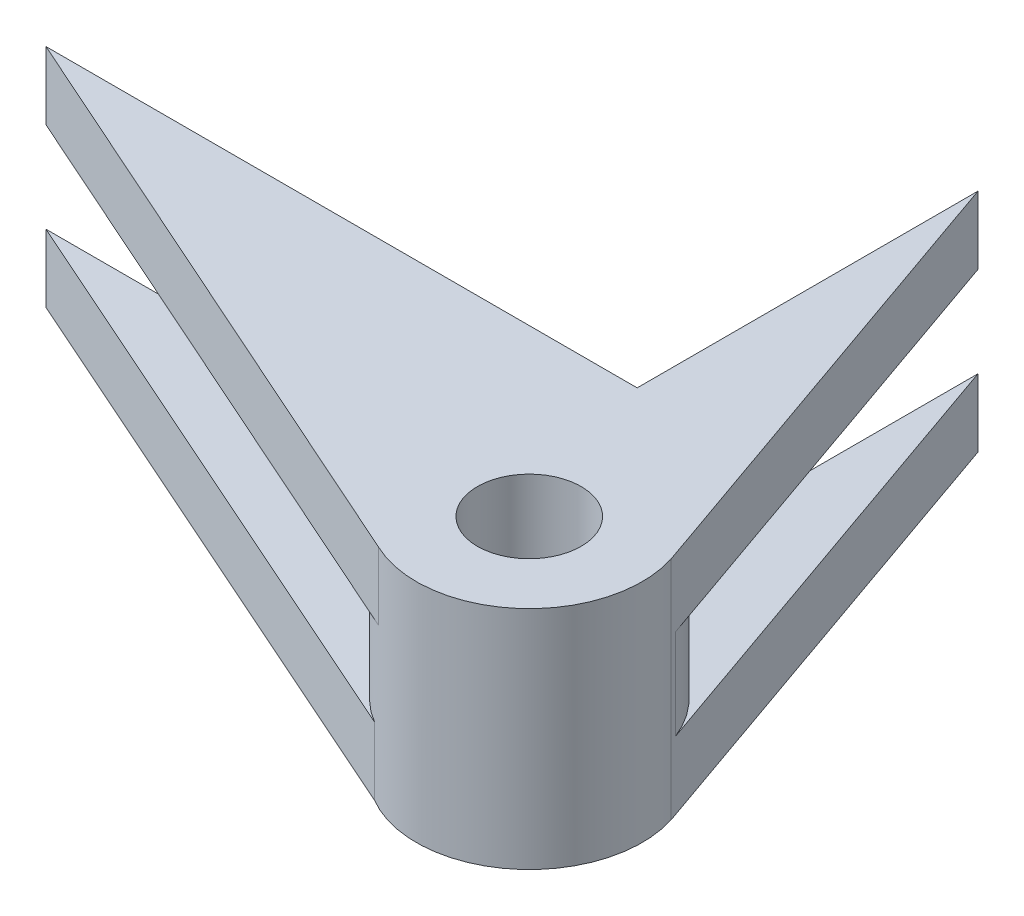
SolidWorks part; units mm, degrees
ref_plane "Front Plane" through (0, 0, 0) normal (0, 0, 1) x (1, 0, 0)
ref_plane "Top Plane" through (0, 0, 0) normal (0, 1, 0) x (1, 0, 0)
ref_plane "Right Plane" through (0, 0, 0) normal (1, 0, 0) x (0, 0, -1)
sketch "Sketch1" plane through (0, 0, 0) normal (0, 1, 0) x (1, 0, 0)
  line L0 (30.5988, 30.1673) -> (30.5988, 0)
  line L1 (30.5988, 30.1673) -> (45.2163, -11.6217)
  line L2 (0, 0) -> (-21.7254, 0)
  line L3 (-21.7254, 0) -> (30.5988, -23.2433)
  line L4 (30.5988, 0) -> (0, 0)
  circle A0 centre (35.6797, -14.6303) radius 10
  circle A1 centre (35.6797, -14.6303) radius 4.5901
  dimension "20" = 20
extrude "Boss-Extrude1" add sketch "Sketch1" along normal blind 6 contours A0 L2 L3 region at (18.2565, 0, 3.1434)
extrude "Boss-Extrude2" add sketch "Sketch1<3>" along normal blind 20 contours A0 A1 region at (44.8474, 0, 11.4234)
sketch "Sketch1<3>" plane through (0, 0, 0) normal (0, 1, 0) x (1, 0, 0) same geometry as "Sketch1"
sketch "Sketch2" plane through (0, 20, 0) normal (0, 1, 0) x (1, 0, 0)
  line L0 (45.1143, -11.33) -> (30.5988, 30.1673)
  line L1 (-21.7254, 0) -> (30.5988, 0)
  line L2 (30.5988, 0) -> (30.5988, 30.1673)
  line L3 (45.0123, -11.0384) -> (45.2163, -11.6217) construction
  line L6 (-21.7254, 0) -> (31.8573, -23.8709)
  circle A0 centre (35.6797, -14.6303) radius 9.9952
  arc A1 (45.0123, -11.0384) -> (45.2163, -11.6217) centre (35.6797, -14.6303) ccw construction
  point P4 (31.8573, -23.8709)
  point P17 (45.1143, -11.33)
  point P20 (0, 0)
  arc M3 (45.0123, -11.0384) -> (45.2163, -11.6217) centre (35.6797, -14.6303) ccw
extrude "Boss-Extrude3" add sketch "Sketch2" against normal blind 6 contours L1 L6 L0 L2 M3 region at (18.2453, 20, 3.172)
